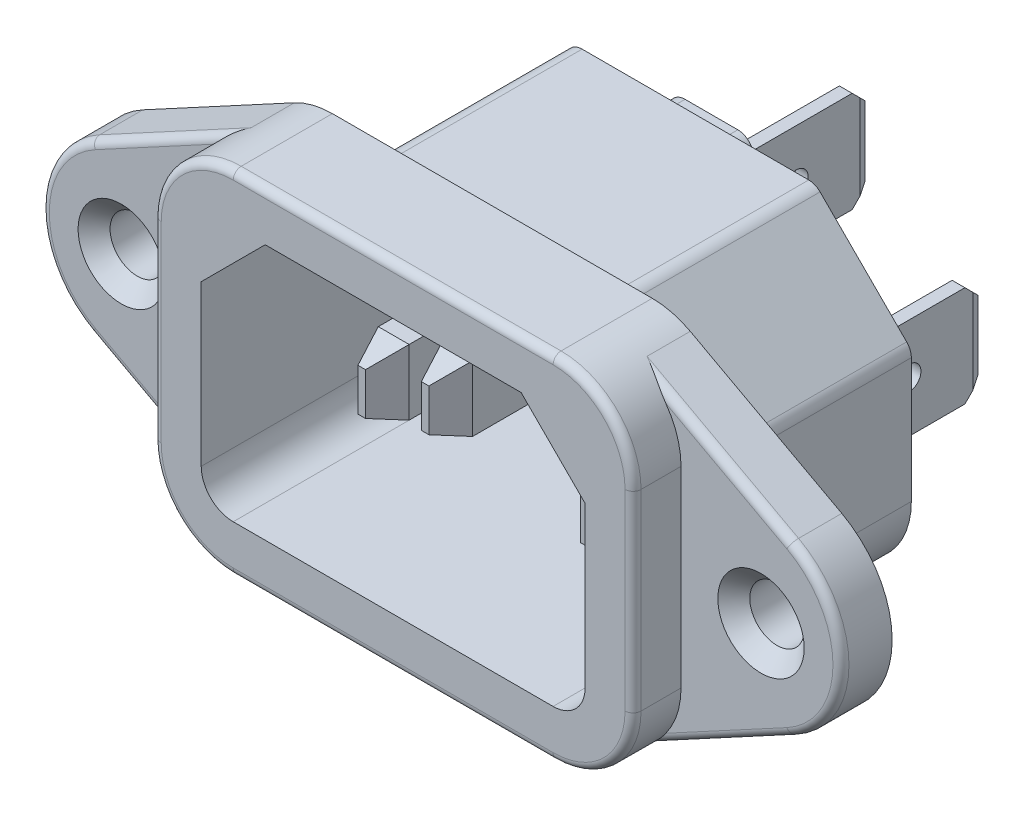
SolidWorks part; units mm, degrees
ref_plane "Front Plane" through (0, 0, 0) normal (0, 0, 1) x (1, 0, 0)
ref_plane "Top Plane" through (0, 0, 0) normal (0, 1, 0) x (1, 0, 0)
ref_plane "Right Plane" through (0, 0, 0) normal (1, 0, 0) x (0, 0, -1)
sketch "Sketch1" plane through (0, 0, 0) normal (0, 0, 1) x (1, 0, 0)
  line L0 (0, 11) -> (-10, 11)
  line L1 (-12.377, 10.3988) -> (-21.8524, 5.2786)
  line L2 (-21.8524, -5.2786) -> (-12.377, -10.3988)
  line L3 (-10, -11) -> (0, -11)
  line L4 (0, 11) -> (0, -11)
  line L5 (0, 0) -> (-19, 0) construction
  line L6 (-10, -11) -> (-10, 11) construction
  line L7 (-12.377, 10.3988) -> (-12.377, -10.3988) construction
  arc A0 (-10, 11) -> (-12.377, 10.3988) centre (-10, 6) ccw
  arc A1 (-10, -11) -> (-12.377, -10.3988) centre (-10, -6) cw
  arc A2 (-21.8524, 5.2786) -> (-21.8524, -5.2786) centre (-19, 0) ccw
  circle A3 centre (-20, 0) radius 1.7
  point P2 (0, 0)
  point P16 (-25, 0)
  dimension "D2" = 5
  dimension "D3" = 6
  dimension "D4" = 3.4
  dimension "D5" = 20
  dimension "D6" = 25
  dimension "D1" = 22
  dimension "D7" = 10
extrude "flange" add sketch "Sketch1" along normal blind 3.2
sketch "Sketch2" plane through (0, 0, 3.2) normal (0, 0, 1) x (1, 0, 0)
  line L1 (0, 11) -> (-10, 11)
  line L2 (0, 11) -> (-10, 11) construction
  line L3 (0, -11) -> (0, 11) construction
  line L4 (-15, 6) -> (-15, -6)
  line L5 (-10, -11) -> (0, -11)
  line L6 (-10, -11) -> (0, -11) construction
  arc A0 (-10, 11) -> (-15, 6) centre (-10, 6) ccw
  arc A2 (-10, -11) -> (-15, -6) centre (-10, -6) cw
  line M1 (0, -11) -> (0, 11)
  line M2 (0, 11) -> (-10, 11)
  line M8 (-10, -11) -> (0, -11)
  dimension "D1" = 5
  dimension "D2" = 15
extrude "top" add sketch "Sketch2" along normal blind 3 contours A2 A0 L4 M8 M1 M2 region at (-7.2855, 0, 3.2)
sketch "Sketch4" plane through (0, 0, 0) normal (0, 0, -1) x (-1, 0, 0)
  line L0 (0, -9.6) -> (8.5, -9.6)
  line L1 (0, -11) -> (0, 11) construction
  line L2 (13.5, -4.6) -> (13.5, 3.1858)
  line L3 (7.0858, 9.6) -> (0, 9.6)
  line L4 (13.2071, 3.8929) -> (7.7929, 9.3071)
  line L5 (0, -9.6) -> (0, 9.6)
  arc A0 (8.5, -9.6) -> (13.5, -4.6) centre (8.5, -4.6) ccw
  arc A1 (7.7929, 9.3071) -> (7.0858, 9.6) centre (7.0858, 8.6) ccw
  arc A2 (13.5, 3.1858) -> (13.2071, 3.8929) centre (12.5, 3.1858) ccw
  point P4 (13.5, 9.6)
  point P10 (0, 0)
  point P14 (7.5, 9.6)
  point P17 (13.5, 3.6)
  dimension "D3" = 5
  dimension "D4" = 1
  dimension "D1" = 19.2
  dimension "D2" = 13.5
extrude "rear" add sketch "Sketch4" along normal blind 12.7
sketch "Sketch3" plane through (0, 0, 6.2) normal (0, 0, 1) x (1, 0, 0)
  line L0 (0, -8) -> (-10, -8)
  line L1 (0, -11) -> (0, 11) construction
  line L2 (-12, -6) -> (-12, 4)
  line L3 (-12, 4) -> (-8, 8)
  line L4 (-8, 8) -> (0, 8)
  line L5 (0, 8) -> (0, -8)
  line L6 (0, 8) -> (0, -8)
  arc A0 (-10, -8) -> (-12, -6) centre (-10, -6) cw
  point P9 (0, 0)
  line M3 (0, -11) -> (0, 11)
  dimension "D3" = 2
  dimension "D1" = 12
  dimension "D2" = 16
  dimension "D4" = 12
  dimension "D5" = 135
extrude "socket" cut sketch "Sketch3" against normal blind 17 contours A0 L0 L4 L3 L2 M3 region at (-5.7701, -0.2558, 6.2)
chamfer "Chamfer2" distance 1 angle 45 1 edges at (-18.3, 0, 3.2)
mirror "Mirror1" about plane through (0, 0, 0) normal (1, 0, 0) of bodies 105
sketch "Sketch5" plane through (0, 0, -10.8) normal (0, 0, 1) x (1, 0, 0)
  line L0 (-6, -1.95) -> (6, -1.95) construction
  line L1 (-7.93, 0.1) -> (-6, 0.1)
  line L2 (-7.93, 0.1) -> (-7.93, -4)
  line L3 (-7.93, -4) -> (-6, -4)
  line L4 (-6, 0.1) -> (-6, -4)
  line L5 (0, 8) -> (0, -8) construction
  line L6 (7.93, 0.1) -> (6, 0.1)
  line L7 (7.93, 0.1) -> (7.93, -4)
  line L8 (7.93, -4) -> (6, -4)
  line L9 (6, 0.1) -> (6, -4)
  line L10 (-0.965, 4.2) -> (0.965, 4.2)
  line L11 (-0.965, 4.2) -> (-0.965, 0.1)
  line L12 (-0.965, 0.1) -> (0.965, 0.1)
  line L13 (0.965, 4.2) -> (0.965, 0.1)
  line L14 (-8, 8) -> (8, 8) construction
  line L15 (10, -8) -> (-10, -8) construction
  point P20 (0, -1.95)
  point P21 (0, 0.1)
  dimension "D1" = 1.93
  dimension "D2" = 4.1
  dimension "D3" = 12
  dimension "D4" = 6.05
extrude "pin" add sketch "Sketch5" along normal blind 12
sketch "Sketch6" plane through (0, 0, 1.2) normal (0, 0, 1) x (1, 0, 0)
  line L4 (-0.965, 4.2) -> (-0.965, 0.1)
  line L5 (-0.965, 0.1) -> (0.965, 0.1)
  line L6 (0.965, 0.1) -> (0.965, 4.2)
  line L7 (0.965, 4.2) -> (-0.965, 4.2)
  line L8 (-0.965, 4.2) -> (-0.965, 0.1)
  line L9 (-0.965, 0.1) -> (0.965, 0.1)
  line L10 (0.965, 0.1) -> (0.965, 4.2)
  line L11 (0.965, 4.2) -> (-0.965, 4.2)
  dimension "D1" = 0
extrude "pinGnd" add sketch "Sketch6" along normal blind 3
chamfer "Chamfer1" distance 2 angle 20 12 edges at (6.965, 0.1, 1.2) (7.93, -1.95, 1.2) (6.965, -4, 1.2) (6, -1.95, 1.2) (-6.965, 0.1, 1.2) (-7.93, -1.95, 1.2) (-6.965, -4, 1.2) (-6, -1.95, 1.2) (0, 4.2, 4.2) (0.965, 2.15, 4.2) (0, 0.1, 4.2) (-0.965, 2.15, 4.2) first distance on face at (6.965, 0.1, -4.8) first distance on face at (7.93, -1.95, -4.8) first distance on face at (6.965, -4, -4.8) first distance on face at (6, -1.95, -4.8) first distance on face at (-6.965, 0.1, -4.8) first distance on face at (-7.93, -1.95, -4.8) first distance on face at (-6.965, -4, -4.8) first distance on face at (-6, -1.95, -4.8) first distance on face at (0, 4.2, -3.3) first distance on face at (0.965, 2.15, -3.3) first distance on face at (0, 0.1, -3.3) first distance on face at (-0.965, 2.15, -3.3)
sketch "Sketch8" plane through (0, 0, -12.7) normal (0, 0, -1) x (-1, 0, 0)
  line L0 (-8.5, -9.6) -> (8.5, -9.6) construction
  line L1 (-8.7, 2.1) -> (-5.4, 2.1)
  line L2 (-9.7, 1.1) -> (-9.7, -8.1)
  line L3 (-8.7, -9.1) -> (-5.4, -9.1)
  line L4 (-4.4, 1.1) -> (-4.4, -8.1)
  arc A0 (-8.7, 2.1) -> (-9.7, 1.1) centre (-8.7, 1.1) ccw
  arc A1 (-4.4, 1.1) -> (-5.4, 2.1) centre (-5.4, 1.1) ccw
  arc A2 (-5.4, -9.1) -> (-4.4, -8.1) centre (-5.4, -8.1) ccw
  arc A3 (-9.7, -8.1) -> (-8.7, -9.1) centre (-8.7, -8.1) ccw
  point P14 (0, -9.6)
  dimension "D1" = 1
  dimension "D2" = 5.3
  dimension "D3" = 11.2
  dimension "D4" = 0.5
  dimension "D5" = 4.4
extrude "Extrude8" add sketch "Sketch8" along normal blind 1
sketch "Sketch9" plane through (0, 0, -12.7) normal (0, 0, -1) x (-1, 0, 0)
  line L0 (-4.4, -8.1) -> (-4.4, 1.1) construction
  line L2 (7.0858, 9.6) -> (-7.0858, 9.6) construction
  point P0 (0, 3.5)
  point P1 (7.05, -3.5)
  point P5 (-4.4, -3.5)
  dimension "D1" = 11.45
  dimension "D2" = 0
  dimension "D3" = 6.1
pattern_sketch "Sketch-Pattern1" of "Extrude8" driven by "Sketch9"
sketch "Sketch10" plane through (0, 0, -13.7) normal (0, 0, -1) x (-1, 0, 0)
  line L0 (7.05, 2.1) -> (7.05, -9.1) construction
  line L1 (0, 6.65) -> (-0.8, 6.65)
  line L2 (0, 6.65) -> (0, 0.35)
  line L3 (0, 0.35) -> (-0.8, 0.35)
  line L4 (-0.8, 6.65) -> (-0.8, 0.35)
  line L5 (7.05, -0.35) -> (6.25, -0.35)
  line L6 (7.05, -0.35) -> (7.05, -6.65)
  line L7 (7.05, -6.65) -> (6.25, -6.65)
  line L8 (6.25, -0.35) -> (6.25, -6.65)
  line L9 (-7.05, -0.35) -> (-7.85, -0.35)
  line L10 (-7.05, -0.35) -> (-7.05, -6.65)
  line L11 (-7.05, -6.65) -> (-7.85, -6.65)
  line L12 (-7.85, -0.35) -> (-7.85, -6.65)
  line L14 (8.7, 2.1) -> (5.4, 2.1) construction
  line L15 (5.4, -9.1) -> (8.7, -9.1) construction
  line L16 (-7.05, 2.1) -> (-7.05, -9.1) construction
  line L17 (-5.4, 2.1) -> (-8.7, 2.1) construction
  line L18 (-8.7, -9.1) -> (-5.4, -9.1) construction
  line L19 (0, 9.1) -> (0, -2.1) construction
  line L20 (1.65, 9.1) -> (-1.65, 9.1) construction
  line L21 (-1.65, -2.1) -> (1.65, -2.1) construction
  point P18 (7.05, -3.5)
  point P25 (-7.05, -3.5)
  point P32 (0, 3.5)
  dimension "D1" = 0.8
  dimension "D2" = 6.3
extrude "rear_blades" add sketch "Sketch10" along normal blind 9
chamfer "blade_chmf" distance 1 angle 45 6 edges at (-6.65, -0.35, -22.7) (-6.65, -6.65, -22.7) (0.4, 6.65, -22.7) (0.4, 0.35, -22.7) (7.45, -0.35, -22.7) (7.45, -6.65, -22.7)
chamfer "blade_chmf2" distance 0.5 angle 20 6 edges at (-7.05, -3.5, -22.7) (-6.25, -3.5, -22.7) (7.85, -3.5, -22.7) (7.05, -3.5, -22.7) (0.8, 3.5, -22.7) (0, 3.5, -22.7) first distance on face at (-7.05, -3.5, -19.3667) first distance on face at (-6.25, -3.5, -19.3667) first distance on face at (7.85, -3.5, -19.3667) first distance on face at (7.05, -3.5, -19.3667) first distance on face at (0.8, 3.5, -19.3667) first distance on face at (0, 3.5, -19.3667)
fillet "Fillet1" radius 0.5 14 edges at (25, 0, 3.2) (-25, 0, 3.2) (0, 11, 6.2) (13.5355, 9.5355, 6.2) (15, 0, 6.2) (13.5355, -9.5355, 6.2) (0, -11, 6.2) (-13.5355, -9.5355, 6.2) (-15, 0, 6.2) (-13.5355, 9.5355, 6.2)
sketch "Sketch11" plane through (-7.05, 0, 0) normal (-1, 0, 0) x (0, 0, 1)
  line L0 (-22.2, -3.5) -> (-18.95, -3.5) construction
  line L1 (-22.2, -0.85) -> (-22.2, -6.15) construction
  line L2 (-18.2, -3.5) -> (-18.2, 3.5) construction
  line L3 (-22.2, 6.15) -> (-22.2, 0.85) construction
  line L4 (-22.2, 6.15) -> (-22.2, 0.85)
  line L5 (-22.2, 3.5) -> (-18.2, 3.5) construction
  circle A0 centre (-18.2, -3.5) radius 0.75
  circle A1 centre (-18.2, 3.5) radius 0.75
  point P6 (-18.95, -3.5)
  dimension "D1" = 1.5
  dimension "D2" = 3.25
extrude "Extrude9" cut sketch "Sketch11" against normal through all contours A0 | A1 region at (-7.05, -3.5, -18.2) region at (-7.05, 3.5, -18.2)
